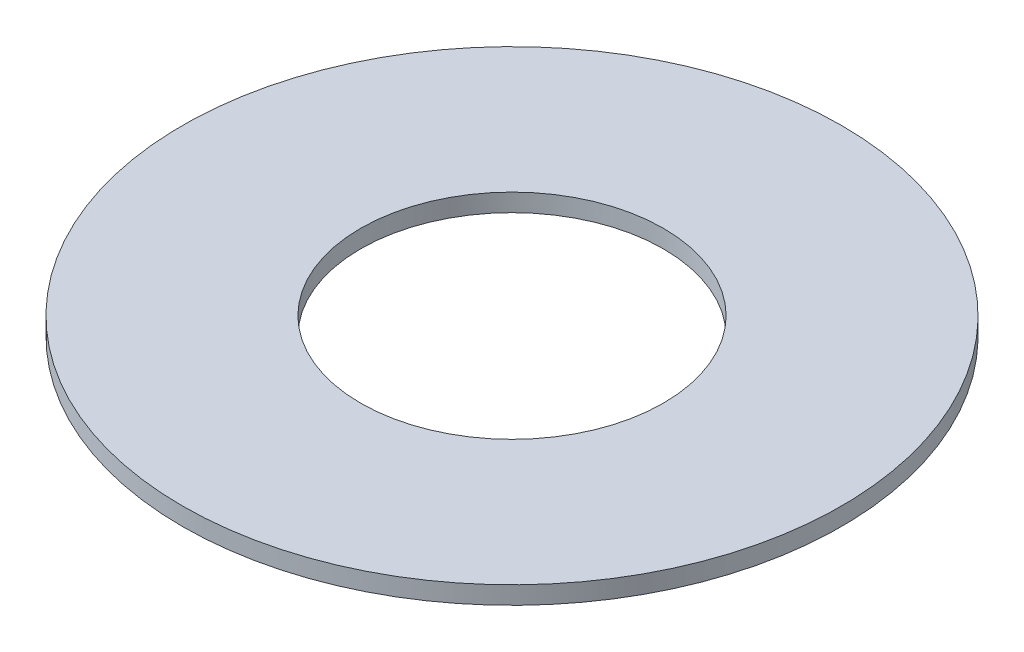
SolidWorks part; units mm, degrees
ref_plane "Front Plane" through (0, 0, 0) normal (0, 0, 1) x (1, 0, 0)
ref_plane "Top Plane" through (0, 0, 0) normal (0, 1, 0) x (1, 0, 0)
ref_plane "Right Plane" through (0, 0, 0) normal (1, 0, 0) x (0, 0, -1)
sketch "Sketch1" plane through (0, 0, 0) normal (0, 1, 0) x (1, 0, 0)
  circle A0 centre (0, 0) radius 92.5
  dimension "FLANGE_OD" = 185
extrude "Boss-Extrude1" add sketch "Sketch1" along normal blind 5
sketch "Sketch2" plane through (0, 0, 0) normal (0, 1, 0) x (1, 0, 0)
  circle A0 centre (0, 0) radius 42.5
  dimension "BORE_D" = 85
extrude "Cut-Extrude1" cut sketch "Sketch2" along normal through all
sketch "Sketch3" plane through (0, 5, 0) normal (0, 1, 0) x (1, 0, 0)
  circle A0 centre (0, 0) radius 34.0255 construction
  circle A1 centre (-34.0255, 0) radius 7.1938
  dimension "BOLT_D" = 14.3876
  dimension "BOLT_PCD" = 68.051
extrude "Cut-Extrude2" cut sketch "Sketch3" against normal blind 3.0584 rebuild error yes
pattern_circular "CirPattern1" count 8 over 360 rebuild error yes
